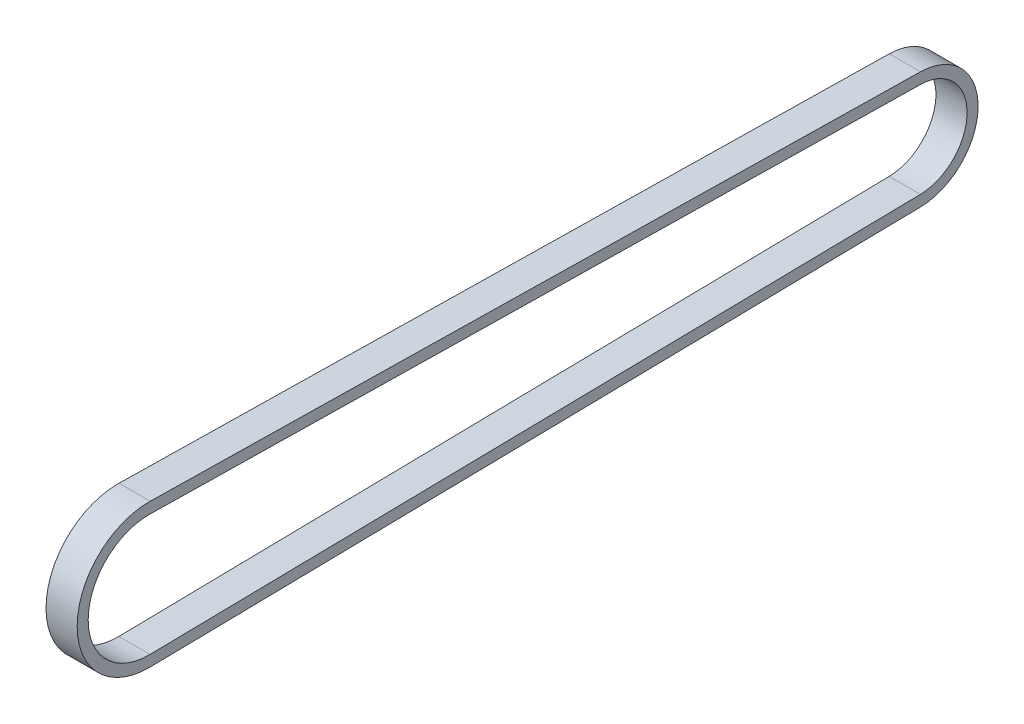
SolidWorks part; units mm, degrees
ref_plane "Front Plane" through (0, 0, 0) normal (0, 0, 1) x (1, 0, 0)
ref_plane "Top Plane" through (0, 0, 0) normal (0, 1, 0) x (1, 0, 0)
ref_plane "Right Plane" through (0, 0, 0) normal (1, 0, 0) x (0, 0, -1)
other "Bounding Box"
ref_plane "Default Plane" through (-8.9266, -12.7485, 0) normal (-0.1736, 0.9848, 0) x (0.9848, 0.1736, 0)
sketch "Sketch1" plane through (0, 0, 0) normal (1, 0, 0) x (0, 0, -1)
  line L0 (0, 0) -> (222.41, 0) construction
  line L1 (0.3014, 17.5463) -> (222.6458, 13.7267)
  line L2 (0.3014, -17.5463) -> (222.6458, -13.7267)
  line L3 (0.356, 20.7208) -> (222.7004, 16.9012)
  line L4 (0.356, -20.7208) -> (222.7004, -16.9012)
  line L5 (-17.5489, 0) -> (-20.7239, 0) construction
  line L6 (236.1387, 0) -> (239.3137, 0) construction
  arc A0 (0.3014, 17.5463) -> (0.3014, -17.5463) centre (0, 0) ccw
  arc A1 (222.6458, -13.7267) -> (222.6458, 13.7267) centre (222.41, 0) ccw
  arc A2 (0.356, 20.7208) -> (0.356, -20.7208) centre (0, 0) ccw
  arc A3 (222.7004, -16.9012) -> (222.7004, 16.9012) centre (222.41, 0) ccw
  dimension "D2" = 3.175
  dimension "D4" = 35.0977
  dimension "D5" = 27.4574
  dimension "D1" = 222.41
extrude "Boss-Extrude1" add sketch "Sketch1" along normal mid plane 9
